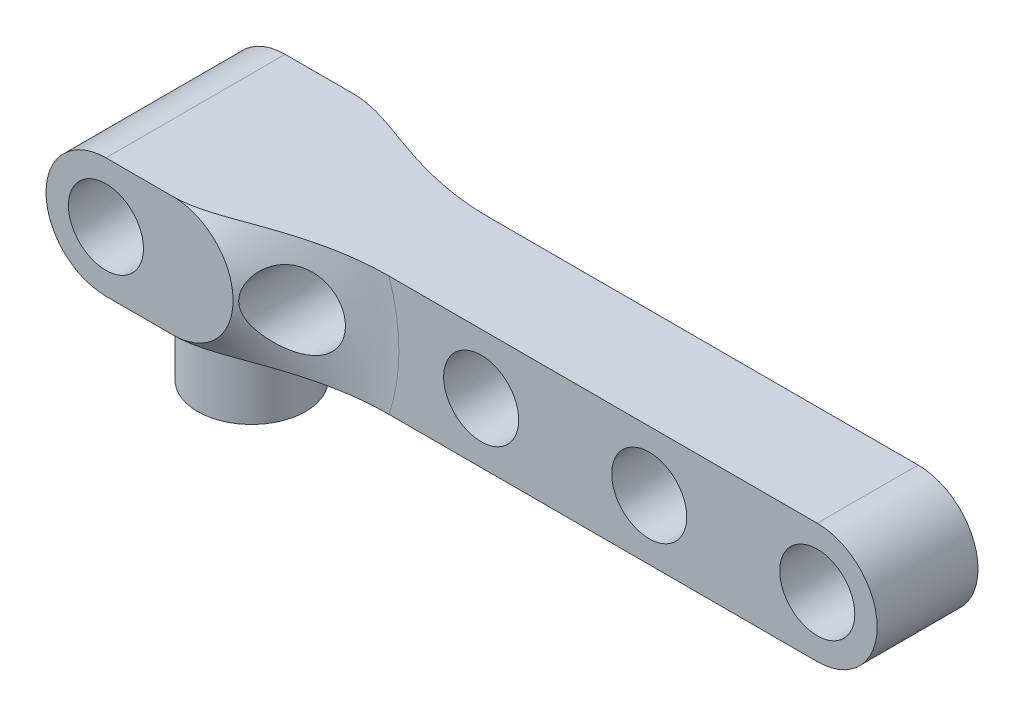
SolidWorks part; units mm, degrees
ref_plane "Front" through (0, 0, 0) normal (0, 0, 1) x (1, 0, 0)
ref_plane "Top" through (0, 0, 0) normal (0, 1, 0) x (1, 0, 0)
ref_plane "Right" through (0, 0, 0) normal (1, 0, 0) x (0, 0, -1)
sketch "Sketch1" plane through (0, 0, 0) normal (0, 0, 1) x (1, 0, 0)
  line L0 (-15, 0) -> (15, 0) construction
  line L1 (-15, 2.675) -> (15, 2.675)
  line L2 (-15, -2.675) -> (15, -2.675)
  arc A0 (-15, 2.675) -> (-15, -2.675) centre (-15, 0) ccw
  arc A1 (15, -2.675) -> (15, 2.675) centre (15, 0) ccw
  circle A2 centre (-15, 0) radius 1.675
  circle A3 centre (-7.5, 0) radius 1.675
  circle A4 centre (0, 0) radius 1.675
  circle A5 centre (7.5, 0) radius 1.675
  circle A6 centre (15, 0) radius 1.675
  point P3 (0, 0)
  dimension "D1" = 3.35
  dimension "D3" = 1
  dimension "D2" = 30
  dimension "D4" = 5
extrude "Boss-Extrude1" add sketch "Sketch1" along normal mid plane 4.5
sketch "Sketch3" plane through (0, 0, 0) normal (0, 0, 1) x (1, 0, 0)
  line L1 (15, 2.675) -> (-15, 2.675) construction
  line L2 (15, 2.675) -> (-15, 2.675)
  line L3 (-15, -2.675) -> (15, -2.675)
  line L4 (-12, 2.675) -> (-15, 2.675)
  line L5 (-15, -2.675) -> (-12, -2.675)
  line L7 (-15, -2.675) -> (15, -2.675) construction
  circle A0 centre (-15, 0) radius 1.675 construction
  circle A1 centre (-15, 0) radius 1.675
  arc A2 (-15, 2.675) -> (-15, -2.675) centre (-15, 0) ccw
  arc A3 (15, -2.675) -> (15, 2.675) centre (15, 0) ccw
  arc A4 (-15, 2.675) -> (-15, -2.675) centre (-15, 0) ccw
  arc A7 (-12, 2.675) -> (-12, -2.675) centre (-12, 0) cw
  dimension "D2" = 3
  dimension "D1" = 0
extrude "Boss-Extrude2" add sketch "Sketch3" along normal mid plane 8
fillet "Fillet1" radius 10 2 edges at (-9.325, 0, -2.25) (-9.325, 0, 2.25)
sketch "Sketch4" plane through (0, -2.675, 0) normal (0, -1, 0) x (1, 0, 0)
  circle A0 centre (-12.5, 0) radius 2.4146
  point P2 (0, 0)
  dimension "D1" = 4.8292
  dimension "D2" = 12.5
extrude "Boss-Extrude3" add sketch "Sketch4" along normal blind 4
